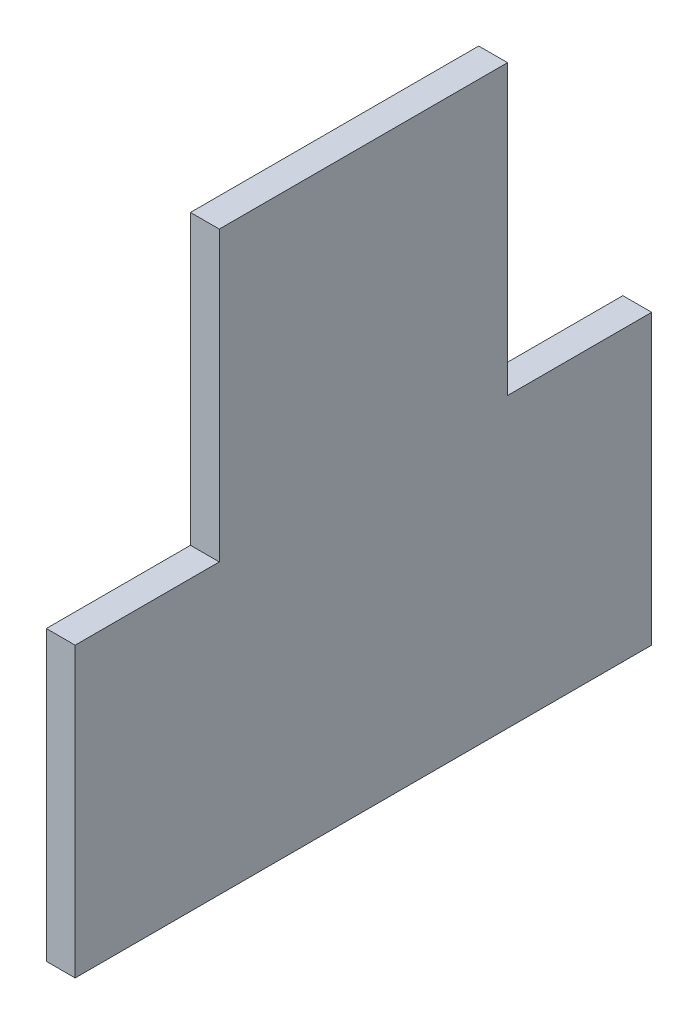
SolidWorks part; units mm, degrees
ref_plane "Front Plane" through (0, 0, 0) normal (0, 0, 1) x (1, 0, 0)
ref_plane "Top Plane" through (0, 0, 0) normal (0, 1, 0) x (1, 0, 0)
ref_plane "Right Plane" through (0, 0, 0) normal (1, 0, 0) x (0, 0, -1)
sketch "Sketch1" plane through (0, 0, 0) normal (0, 1, 0) x (1, 0, 0)
  line L1 (0, 0) -> (12.7, 0)
  line L2 (0, 0) -> (0, 152.4)
  line L3 (0, 152.4) -> (12.7, 152.4)
  line L4 (12.7, 0) -> (12.7, 152.4)
  dimension "D1" = 12.7
  dimension "D2" = 152.4
extrude "Boss-Extrude1" add sketch "Sketch1" along normal blind 25.4
sketch "Sketch6" plane through (12.7, 0, 0) normal (1, 0, 0) x (0, 0, -1)
  line L0 (0, 25.4) -> (152.4, 25.4) construction
  line L1 (152.4, 0) -> (101.6, 0)
  line L2 (152.4, 0) -> (152.4, 25.4)
  line L3 (152.4, 25.4) -> (101.6, 25.4)
  line L4 (101.6, 0) -> (101.6, 25.4)
  dimension "D1" = 50.8
extrude "Boss-Extrude5" add sketch "Sketch6" along normal blind 2.54 contours L2 L1 L4 L3
sketch "Sketch7" plane through (0, 25.4, 0) normal (0, 1, 0) x (1, 0, 0)
  line L0 (12.7, 101.6) -> (12.7, 152.4) construction
  line L1 (15.24, 152.4) -> (0, 152.4) construction
  line L3 (15.24, 152.4) -> (15.24, 101.6) construction
  line L4 (12.7, 114.3) -> (15.24, 114.3)
  line L5 (12.7, 114.3) -> (12.7, 139.7)
  line L6 (12.7, 139.7) -> (15.24, 139.7)
  line L7 (15.24, 114.3) -> (15.24, 139.7)
  point P8 (12.7, 127)
extrude "Boss-Extrude6" add sketch "Sketch7" along normal blind 25.4
sketch "Sketch11" plane through (0, 0, 0) normal (0, 0, 1) x (1, 0, 0)
  line L1 (0, 25.4) -> (12.7, 25.4)
  line L2 (0, 25.4) -> (0, 0)
  line L3 (0, 0) -> (12.7, 0)
  line L4 (12.7, 25.4) -> (12.7, 0)
extrude "Cut-Extrude1" cut sketch "Sketch11" against normal through all
